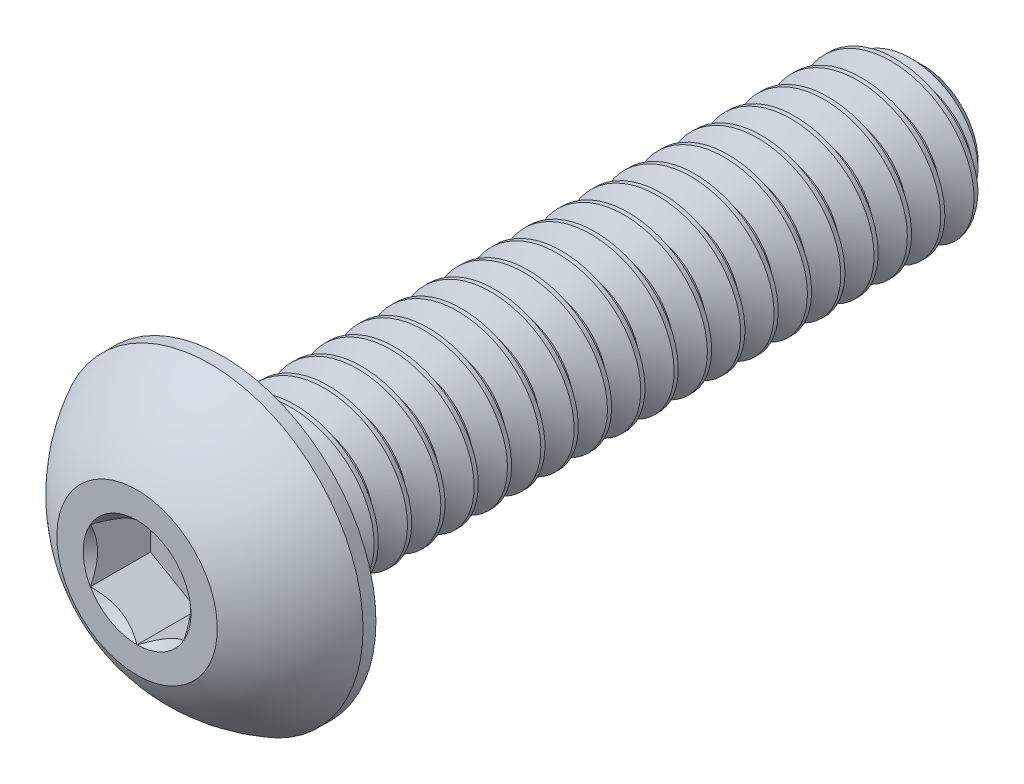
SolidWorks part; units mm, degrees
ref_plane "Front" through (0, 0, 0) normal (0, 0, 1) x (1, 0, 0)
ref_plane "Top" through (0, 0, 0) normal (0, 1, 0) x (1, 0, 0)
ref_plane "Right" through (0, 0, 0) normal (1, 0, 0) x (0, 0, -1)
sketch "Sketch1" plane through (0, 0, 0) normal (1, 0, 0) x (0, 0, -1)
  line L2 (1.1684, 1.0922) -> (10.6934, 1.0922)
  line L3 (10.6934, 1.0922) -> (10.6934, 0)
  line L4 (10.6934, 0) -> (1.1684, 0)
  line L6 (0.9931, 2.0828) -> (1.1684, 2.0828) construction
  line L7 (10.6934, 1.0922) -> (10.6934, -1.0922) construction
  line L8 (0, 0) -> (1.1684, 0) construction
  line L9 (1.1684, 2.0828) -> (1.1684, -2.0828) construction
  line L11 (1.1684, 1.0922) -> (1.1684, 0)
  line L13 (0, 0.635) -> (0, -0.635) construction
  line L14 (0, 0.635) -> (0, 1.0922) construction
  arc A3 (0, 1.0922) -> (0.9931, 2.0828) centre (2.08, 0) cw construction
  dimension "D1" = 0.1753
revolve "Revolve1" add sketch "Sketch1" angle 360 mid plane about L4
sketch "Sketch3" plane through (0, 0, -10.6934) normal (0, 0, -1) x (-1, 0, 0)
  circle A0 centre (0, 0) radius 1.0922
curve "Helix/Spiral1" pitch 0.4536 height 9.9786 radius 1.0922 centre (0, 0, -10.6934) axis (0, 0, 1) start towards (0, 1, 0)
sketch "Sketch2" plane through (0, 0, 0) normal (1, 0, 0) x (0, 0, -1)
  line L0 (10.6934, 1.0922) -> (11.0903, 1.0922)
  line L1 (11.0903, 1.0922) -> (10.9202, 0.7976)
  line L2 (10.9202, 0.7976) -> (10.8635, 0.7976)
  line L3 (10.8635, 0.7976) -> (10.6934, 1.0922)
  line L4 (10.7784, 0.9449) -> (11.0052, 0.9449) construction
  dimension "D1" = 60
  dimension "D2" = 0.0567
  dimension "D3" = 0.2268
chamfer "Chamfer1" distance 0.3402 angle 45 1 edges at (0, 1.0922, -10.6934)
sweep "Cut-Sweep1" cut profiles "Sketch2" path "Helix/Spiral1" align with end faces yes
sketch "Sketch7" plane through (0, 0, 0) normal (1, 0, 0) x (0, 0, -1)
  line L6 (0.9931, 2.0828) -> (1.1684, 2.0828) construction
  line L8 (0, 0) -> (1.1684, 0) construction
  line L11 (1.1684, 2.0828) -> (1.1684, -2.0828) construction
  line L12 (0.9931, 2.0828) -> (1.1684, 2.0828)
  line L13 (0, 0) -> (1.1684, 0)
  line L14 (0, 0.635) -> (0, -0.635) construction
  line L15 (1.1684, 2.0828) -> (1.1684, 0)
  line L16 (0, 1.0922) -> (0, 0)
  arc A2 (0.9931, 2.0828) -> (0, 1.0922) centre (2.08, 0) ccw construction
  arc A3 (0.9931, 2.0828) -> (0, 1.0922) centre (2.08, 0) ccw
revolve "Revolve2" add sketch "Sketch7" angle 360 mid plane about L13
sketch "Sketch5" plane through (0, 0, 0) normal (0, 0, 1) x (1, 0, 0)
  line L1 (0.635, -0.3666) -> (0.635, 0.3666)
  line L2 (0.635, 0.3666) -> (0, 0.7332)
  line L3 (0, 0.7332) -> (-0.635, 0.3666)
  line L4 (-0.635, 0.3666) -> (-0.635, -0.3666)
  line L5 (-0.635, -0.3666) -> (0, -0.7332)
  line L6 (0, -0.7332) -> (0.635, -0.3666)
  circle A0 centre (0, 0) radius 0.635 construction
extrude "Cut-Extrude2" cut sketch "Sketch5" against normal blind 0.8179
sketch "Sketch6" plane through (0, 0, 0) normal (0, 0, 1) x (1, 0, 0)
  circle A0 centre (0, 0) radius 0.7332
extrude "Cut-Extrude3" cut sketch "Sketch6" against normal blind 0.8179 draft 45
sketch "Sketch9" [suppressed] plane through (0, 0, -1.1684) normal (0, 0, 1) x (1, 0, 0)
  circle A2 centre (0, 0) radius 1.0922
extrude "Boss-Extrude2" [suppressed] add sketch "Sketch9" against normal offset from surface (6.35 mm away) 31.75 up to face at (0, 0.752, -10.6934)
sketch "Sketch10" plane through (0, 0, 0) normal (1, 0, 0) x (0, 0, -1)
  line L0 (10.6934, 1.0922) -> (10.6934, -1.0922) construction
  point P0 (10.013, -1.0922)
  dimension "D1" = 0.6804
equation "\"D3@Helix/Spiral1\" = \"Lg@Sketch1\" + \"D4@Helix/Spiral1\""
equation "\"D2@Sketch2\" = \"D4@Helix/Spiral1\" * .125"
equation "\"D3@Sketch2\" = \"D4@Helix/Spiral1\" * .5"
equation "\"D1@Chamfer1\" = \"D4@Helix/Spiral1\" * .75"
equation "\"D1@Cut-Extrude2\" = \"Head Ht@Sketch1\" * .7"
equation "\"D1@Sketch1\" = \"Head Ht@Sketch1\" * .15"
equation "\"D1@Sketch10\" = \"D4@Helix/Spiral1\" * 1.5"
equation "\"D1@Cut-Extrude3\" = \"D1@Cut-Extrude2\""
